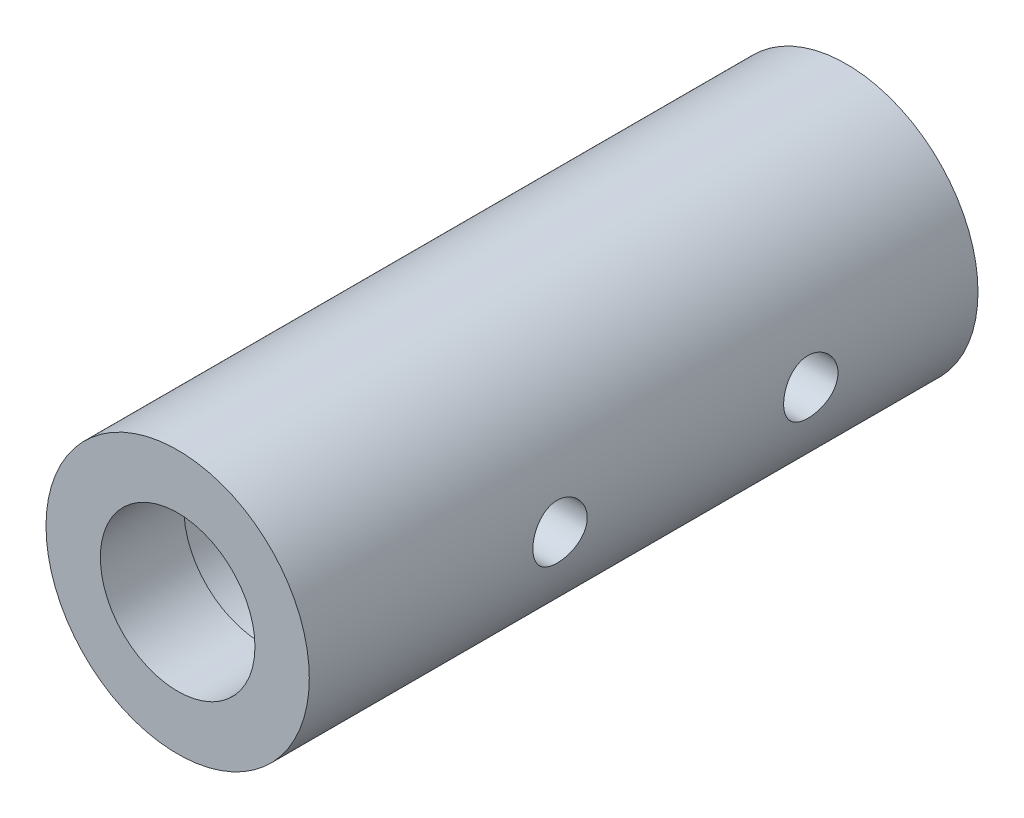
SolidWorks part; units mm, degrees
ref_plane "Front Plane" through (0, 0, 0) normal (0, 0, 1) x (1, 0, 0)
ref_plane "Top Plane" through (0, 0, 0) normal (0, 1, 0) x (1, 0, 0)
ref_plane "Right Plane" through (0, 0, 0) normal (1, 0, 0) x (0, 0, -1)
sketch "Sketch1" plane through (0, 0, 0) normal (0, 0, 1) x (1, 0, 0)
  circle A0 centre (0, 0) radius 4.2
  circle A1 centre (0, 0) radius 6.3
  dimension "D1" = 8.4
  dimension "D2" = 12.6
extrude "Boss-Extrude1" add sketch "Sketch1" along normal blind 16 and the other way blind 16
sketch "Sketch2" plane through (0, 0, 0) normal (1, 0, 0) x (0, 0, -1)
  line L0 (-16, 6.3) -> (-16, -6.3) construction
  line L1 (16, -6.3) -> (16, 6.3) construction
  circle A0 centre (-4, 0) radius 1.3
  circle A1 centre (8, 0) radius 1.3
  dimension "D1" = 2.6
  dimension "D3" = 2.6
  dimension "D2" = 12
  dimension "D4" = 8
extrude "Cut-Extrude1" cut sketch "Sketch2" against normal blind 10 and the other way blind 14
sketch "Sketch3" plane through (0, 0, 16) normal (0, 0, 1) x (1, 0, 0)
  circle A0 centre (0, 0) radius 4.2 construction
  circle A1 centre (0, 0) radius 4.2
  circle A2 centre (0, 0) radius 3.7
  dimension "D1" = 7.4
extrude "Boss-Extrude2" add sketch "Sketch3" against normal blind 4
